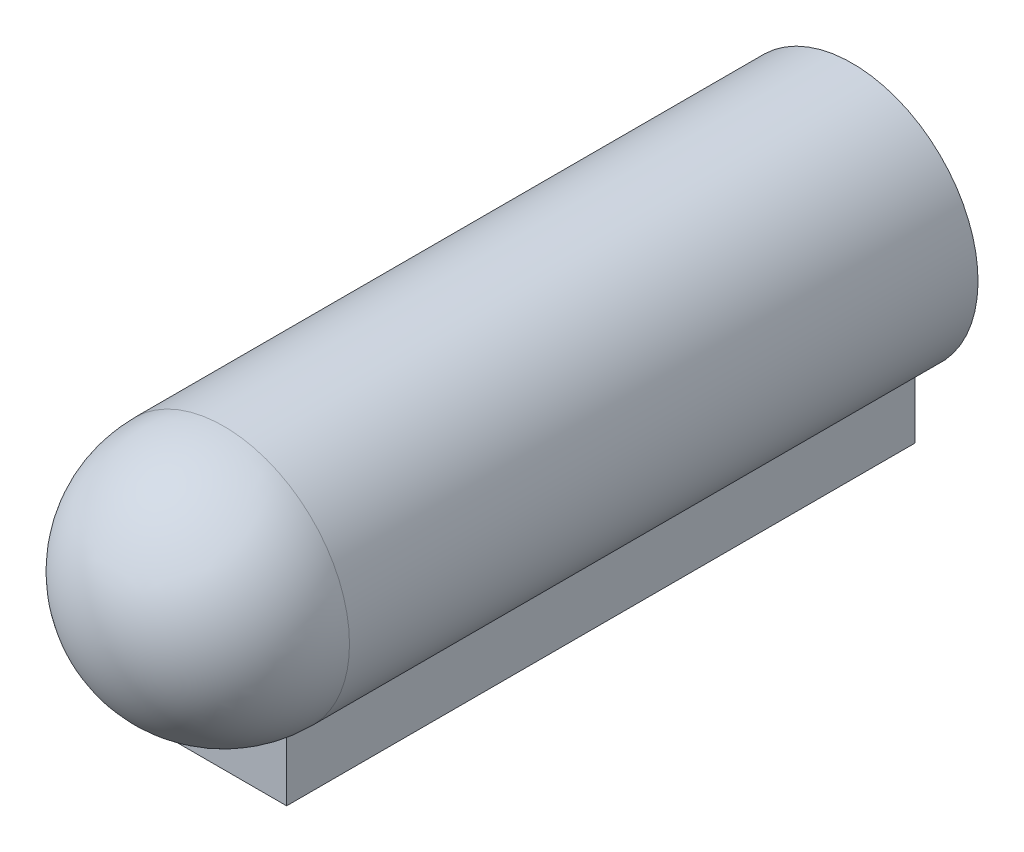
SolidWorks part; units mm, degrees
ref_plane "Płaszczyzna przednia" through (0, 0, 0) normal (0, 0, 1) x (1, 0, 0)
ref_plane "Płaszczyzna górna" through (0, 0, 0) normal (0, 1, 0) x (1, 0, 0)
ref_plane "Płaszczyzna prawa" through (0, 0, 0) normal (1, 0, 0) x (0, 0, -1)
sketch "Szkic1" plane through (0, 0, 0) normal (0, 0, 1) x (1, 0, 0)
  circle A0 centre (0, 0) radius 5
  circle A1 centre (0, 0) radius 3
  dimension "D1" = 10
  dimension "D2" = 2
extrude "Dodanie-wyciągnięcie1" add sketch "Szkic1" along normal blind 30 contours A1 | A0 A1 region at (-4.8586, 0, 0) region at (0, 0, 0)
extrude "Wytnij-wyciągnięcie1" cut sketch "Szkic1<3>" along normal blind 20 contours A1 region at (0, 0, 0)
sketch "Szkic1<3>" plane through (0, 0, 0) normal (0, 0, 1) x (1, 0, 0) same geometry as "Szkic1"
fillet "Zaokrąglenie1" radius 5 1 edges at (5, 0, 30)
sketch "Szkic4" plane through (0, 0, 0) normal (0, 0, -1) x (-1, 0, 0)
  line L0 (-2.5, -4.3301) -> (-2.5, -6.8301)
  line L1 (-2.5, -6.8301) -> (2.5, -6.8301)
  line L2 (2.5, -6.8301) -> (2.5, -4.3301)
  circle A0 centre (0, 0) radius 5 construction
  circle A1 centre (0, 0) radius 5
  circle A2 centre (0, 0) radius 5
  arc A3 (2.5, -4.3301) -> (-2.5, -4.3301) centre (0, 0) ccw
  circle M8 centre (0, 0) radius 5
  dimension "D1" = 5
  dimension "D2" = 2.5
  dimension "D3" = 2.5
  dimension "D4" = 0
extrude "Dodanie-wyciągnięcie2" add sketch "Szkic4" against normal blind 25 contours L1 L2 L0 M8 region at (0, -5.7971, 0)
